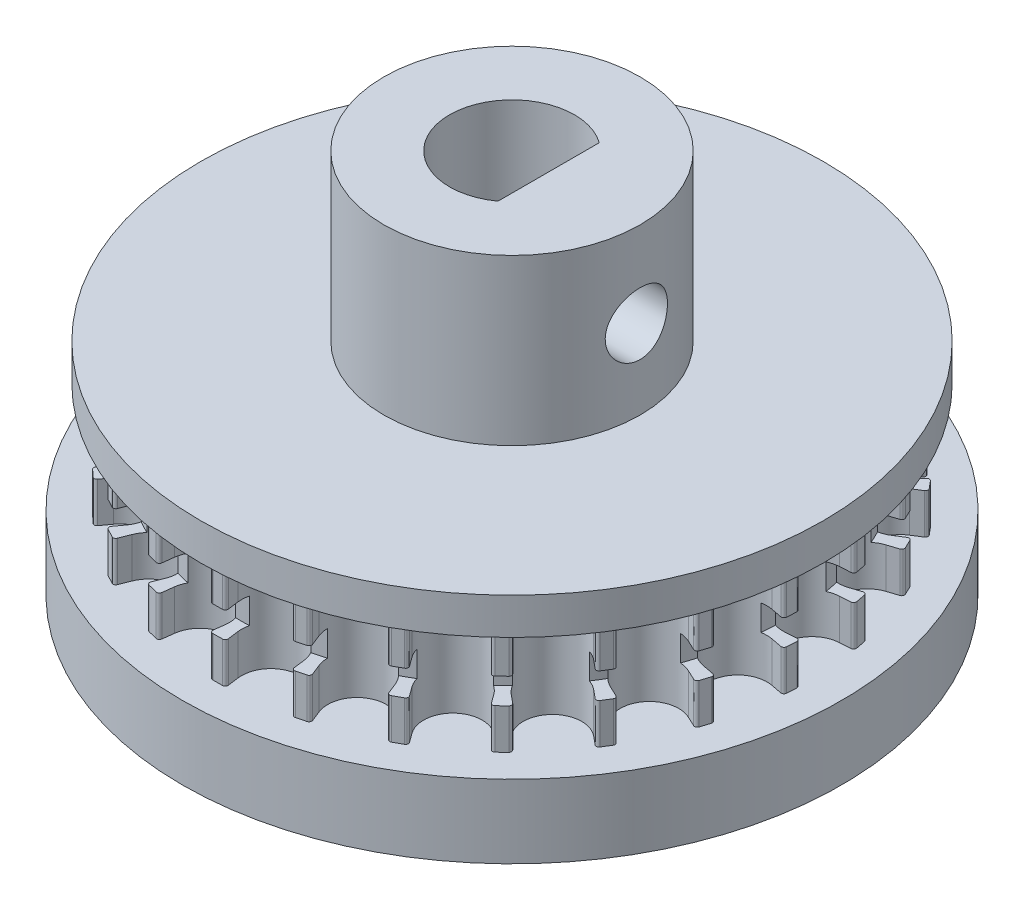
SolidWorks part; units mm, degrees
ref_plane "Спереди" through (0, 0, 0) normal (0, 0, 1) x (1, 0, 0)
ref_plane "Сверху" through (0, 0, 0) normal (0, 1, 0) x (1, 0, 0)
ref_plane "Справа" through (0, 0, 0) normal (1, 0, 0) x (0, 0, -1)
sketch "Sketch1" plane through (0, 0, 0) normal (0, 1, 0) x (1, 0, 0)
  circle A0 centre (0, 0) radius 18
extrude "Boss-Extrude1" add sketch "Sketch1" along normal blind 4
sketch "Sketch7" plane through (0, 4, 0) normal (0, 1, 0) x (1, 0, 0)
  line L25 (2.2991, 15.8675) -> (2.15, 15.2867)
  line L26 (5.4051, 15.097) -> (5.2495, 14.4909)
  line L27 (6.173, 14.7972) -> (5.8841, 14.2718)
  line L28 (-1.7192, 15.9408) -> (-1.7192, 15.3411)
  line L29 (1.4808, 15.9669) -> (1.4808, 15.3411)
  line L30 (8.9898, 13.2785) -> (8.6883, 12.7302)
  line L31 (9.659, 12.7972) -> (9.2485, 12.3601)
  line L32 (12.0096, 10.6257) -> (11.5812, 10.1695)
  line L33 (12.5381, 9.9931) -> (12.0318, 9.6717)
  line L34 (14.2748, 7.3052) -> (13.7464, 6.9699)
  line L35 (14.6293, 6.561) -> (14.059, 6.3757)
  line L36 (15.6431, 3.5257) -> (15.0479, 3.3323)
  line L37 (15.8014, 2.7167) -> (15.2029, 2.6791)
  line L38 (16.0284, -0.4753) -> (15.4038, -0.5146)
  line L39 (15.9806, -1.2983) -> (15.3915, -1.1859)
  line L40 (15.4066, -4.4465) -> (14.7919, -4.3292)
  line L41 (15.1556, -5.2317) -> (14.6131, -4.9764)
  line L42 (13.8168, -8.1383) -> (13.2506, -7.8718)
  line L43 (13.3784, -8.8364) -> (12.9164, -8.4542)
  line L44 (11.3588, -11.3187) -> (10.8766, -10.9198)
  line L45 (10.7606, -11.8859) -> (10.4081, -11.4007)
  line L46 (8.1871, -13.7879) -> (7.8193, -13.2816)
  line L47 (7.4666, -14.1885) -> (7.2459, -13.631)
  line L48 (4.501, -15.3908) -> (4.2706, -14.809)
  line L49 (3.7035, -15.5996) -> (3.6284, -15.0047)
  line L50 (0.532, -16.0266) -> (0.4536, -15.4058)
  line L51 (-0.2923, -16.0306) -> (-0.2171, -15.4356)
  line L52 (-3.4703, -15.6554) -> (-3.3919, -15.0346)
  line L53 (-4.2697, -15.4542) -> (-4.049, -14.8967)
  line L54 (-7.2547, -14.3006) -> (-7.0243, -13.7187)
  line L55 (-7.9789, -13.9069) -> (-7.6265, -13.4218)
  line L56 (-10.5831, -12.0471) -> (-10.2153, -11.5408)
  line L57 (-11.1867, -11.4857) -> (-10.7247, -11.1035)
  line L58 (-13.2466, -9.0367) -> (-12.7645, -8.6378)
  line L59 (-13.6917, -8.3428) -> (-13.1491, -8.0875)
  line L60 (-15.0778, -5.4585) -> (-14.5116, -5.1921)
  line L61 (-15.3363, -4.6757) -> (-14.7473, -4.5634)
  line L62 (-15.9616, -1.5373) -> (-15.3469, -1.4201)
  line L63 (-16.0173, -0.7149) -> (-15.4188, -0.7525)
  line L64 (-15.8424, 2.4805) -> (-15.2179, 2.4412)
  line L65 (-15.6918, 3.2909) -> (-15.1215, 3.1056)
  line L66 (-14.7279, 6.3424) -> (-14.1327, 6.149)
  line L67 (-14.3804, 7.0899) -> (-13.8741, 6.7686)
  line L68 (-12.6879, 9.8058) -> (-12.1595, 9.4705)
  line L69 (-12.1654, 10.4435) -> (-11.755, 10.0064)
  line L70 (-9.8506, 12.6531) -> (-9.4223, 12.1969)
  line L71 (-9.1861, 13.1408) -> (-8.8972, 12.6153)
  line L72 (-6.3945, 14.7053) -> (-6.093, 14.1569)
  line L73 (-5.6295, 15.0124) -> (-5.4804, 14.4316)
  line L74 (-2.5365, 15.8336) -> (-2.3809, 15.2274)
  line L75 (1.6461, 16.1162) -> (2.174, 16.0535)
  line L76 (5.6023, 15.2005) -> (6.098, 15.0085)
  line L77 (9.2065, 13.3297) -> (9.6389, 13.0204)
  line L78 (12.2322, 10.6214) -> (12.5741, 10.2143)
  line L79 (14.4893, 7.2457) -> (14.7193, 6.7663)
  line L80 (15.836, 3.4147) -> (15.9396, 2.8932)
  line L81 (16.1877, -0.6309) -> (16.1583, -1.1617)
  line L82 (15.5223, -4.6368) -> (15.3618, -5.1436)
  line L83 (13.8815, -8.3513) -> (13.6, -8.8023)
  line L84 (11.3685, -11.5411) -> (10.9837, -11.9079)
  line L85 (8.1411, -14.0058) -> (7.6772, -14.2654)
  line L86 (4.4023, -15.5904) -> (3.8884, -15.7264)
  line L87 (0.3868, -16.1954) -> (-0.1448, -16.1994)
  line L88 (-3.653, -15.7828) -> (-4.1689, -15.6544)
  line L89 (-7.4632, -14.3785) -> (-7.931, -14.1258)
  line L90 (-10.8045, -12.0707) -> (-11.1948, -11.7097)
  line L91 (-13.467, -9.0045) -> (-13.7552, -8.5578)
  line L92 (-15.2832, -5.3725) -> (-15.4512, -4.8682)
  line L93 (-16.1391, -1.403) -> (-16.1765, -0.8726)
  line L94 (-15.981, 2.6548) -> (-15.8853, 3.1777)
  line L95 (-14.8187, 6.5457) -> (-14.596, 7.0284)
  line L96 (-12.7253, 10.0253) -> (-12.3895, 10.4374)
  line L97 (-9.8323, 12.875) -> (-9.4046, 13.1907)
  line L98 (-6.3216, 14.9157) -> (-5.8287, 15.1151)
  line L99 (-2.4136, 16.0192) -> (-1.8866, 16.0898)
  arc A16 (13.7013, 6.2878) -> (13.8151, 6.4563) centre (13.6668, 6.4337) ccw
  arc A75 (-1.7192, 15.3411) -> (1.4808, 15.3411) centre (-0.1192, 15.3411) ccw
  arc A76 (2.2991, 15.8675) -> (2.174, 16.0535) centre (2.1539, 15.9048) ccw
  arc A77 (-1.7192, 15.9408) -> (-1.8866, 16.0898) centre (-1.8692, 15.9408) ccw
  arc A78 (1.6461, 16.1162) -> (1.4808, 15.9669) centre (1.6308, 15.9669) ccw
  arc A79 (2.15, 15.2867) -> (5.2495, 14.4909) centre (3.6998, 14.8888) ccw
  arc A80 (5.6023, 15.2005) -> (5.4051, 15.097) centre (5.5504, 15.0597) ccw
  arc A81 (6.173, 14.7972) -> (6.098, 15.0085) centre (6.0416, 14.8695) ccw
  arc A82 (5.8841, 14.2718) -> (8.6883, 12.7302) centre (7.2862, 13.501) ccw
  arc A83 (9.2065, 13.3297) -> (8.9898, 13.2785) centre (9.1212, 13.2063) ccw
  arc A84 (9.659, 12.7972) -> (9.6389, 13.0204) centre (9.5496, 12.8999) ccw
  arc A85 (9.2485, 12.3601) -> (11.5812, 10.1695) centre (10.4149, 11.2648) ccw
  arc A86 (12.2322, 10.6214) -> (12.0096, 10.6257) centre (12.1189, 10.523) ccw
  arc A87 (12.5381, 9.9931) -> (12.5741, 10.2143) centre (12.4577, 10.1197) ccw
  arc A88 (12.0318, 9.6717) -> (13.7464, 6.9699) centre (12.8891, 8.3208) ccw
  arc A89 (14.4893, 7.2457) -> (14.2748, 7.3052) centre (14.3552, 7.1786) ccw
  arc A90 (14.6293, 6.561) -> (14.7193, 6.7663) centre (14.583, 6.7037) ccw
  arc A91 (14.059, 6.3757) -> (15.0479, 3.3323) centre (14.5535, 4.854) ccw
  arc A92 (15.836, 3.4147) -> (15.6431, 3.5257) centre (15.6894, 3.3831) ccw
  arc A93 (15.8014, 2.7167) -> (15.9396, 2.8932) centre (15.792, 2.8664) ccw
  arc A94 (15.2029, 2.6791) -> (15.4038, -0.5146) centre (15.3034, 1.0822) ccw
  arc A95 (16.1877, -0.6309) -> (16.0284, -0.4753) centre (16.0378, -0.625) ccw
  arc A96 (15.9806, -1.2983) -> (16.1583, -1.1617) centre (16.0087, -1.1509) ccw
  arc A97 (15.3915, -1.1859) -> (14.7919, -4.3292) centre (15.0917, -2.7576) ccw
  arc A98 (15.5223, -4.6368) -> (15.4066, -4.4465) centre (15.3785, -4.5938) ccw
  arc A99 (15.1556, -5.2317) -> (15.3618, -5.1436) centre (15.2195, -5.096) ccw
  arc A100 (14.6131, -4.9764) -> (13.2506, -7.8718) centre (13.9318, -6.4241) ccw
  arc A101 (13.8815, -8.3513) -> (13.8168, -8.1383) centre (13.7529, -8.274) ccw
  arc A102 (13.3784, -8.8364) -> (13.6, -8.8023) centre (13.474, -8.7208) ccw
  arc A103 (12.9164, -8.4542) -> (10.8766, -10.9198) centre (11.8965, -9.687) ccw
  arc A104 (11.3685, -11.5411) -> (11.3588, -11.3187) centre (11.2632, -11.4343) ccw
  arc A105 (10.7606, -11.8859) -> (10.9837, -11.9079) centre (10.882, -11.7977) ccw
  arc A106 (10.4081, -11.4007) -> (7.8193, -13.2816) centre (9.1137, -12.3412) ccw
  arc A107 (8.1411, -14.0058) -> (8.1871, -13.7879) centre (8.0658, -13.8761) ccw
  arc A108 (7.4666, -14.1885) -> (7.6772, -14.2654) centre (7.6061, -14.1333) ccw
  arc A109 (7.2459, -13.631) -> (4.2706, -14.809) centre (5.7583, -14.22) ccw
  arc A110 (4.4023, -15.5904) -> (4.501, -15.3908) centre (4.3615, -15.446) ccw
  arc A111 (3.7035, -15.5996) -> (3.8884, -15.7264) centre (3.8524, -15.5808) ccw
  arc A112 (3.6284, -15.0047) -> (0.4536, -15.4058) centre (2.041, -15.2052) ccw
  arc A113 (0.3868, -16.1954) -> (0.532, -16.0266) centre (0.3832, -16.0454) ccw
  arc A114 (-0.2923, -16.0306) -> (-0.1448, -16.1994) centre (-0.1435, -16.0494) ccw
  arc A115 (-0.2171, -15.4356) -> (-3.3919, -15.0346) centre (-1.8045, -15.2351) ccw
  arc A116 (-3.653, -15.7828) -> (-3.4703, -15.6554) centre (-3.6191, -15.6366) ccw
  arc A117 (-4.2697, -15.4542) -> (-4.1689, -15.6544) centre (-4.1303, -15.5095) ccw
  arc A118 (-4.049, -14.8967) -> (-7.0243, -13.7187) centre (-5.5366, -14.3077) ccw
  arc A119 (-7.4632, -14.3785) -> (-7.2547, -14.3006) centre (-7.3941, -14.2453) ccw
  arc A120 (-7.9789, -13.9069) -> (-7.931, -14.1258) centre (-7.8576, -13.995) ccw
  arc A121 (-7.6265, -13.4218) -> (-10.2153, -11.5408) centre (-8.9209, -12.4813) ccw
  arc A122 (-10.8045, -12.0707) -> (-10.5831, -12.0471) centre (-10.7045, -11.9589) ccw
  arc A123 (-11.1867, -11.4857) -> (-11.1948, -11.7097) centre (-11.0911, -11.6013) ccw
  arc A124 (-10.7247, -11.1035) -> (-12.7645, -8.6378) centre (-11.7446, -9.8706) ccw
  arc A125 (-13.467, -9.0045) -> (-13.2466, -9.0367) centre (-13.3423, -8.9211) ccw
  arc A126 (-13.6917, -8.3428) -> (-13.7552, -8.5578) centre (-13.6278, -8.4785) ccw
  arc A127 (-13.1491, -8.0875) -> (-14.5116, -5.1921) centre (-13.8303, -6.6398) ccw
  arc A128 (-15.2832, -5.3725) -> (-15.0778, -5.4585) centre (-15.1417, -5.3228) ccw
  arc A129 (-15.3363, -4.6757) -> (-15.4512, -4.8682) centre (-15.3082, -4.8231) ccw
  arc A130 (-14.7473, -4.5634) -> (-15.3469, -1.4201) centre (-15.0471, -2.9917) ccw
  arc A131 (-16.1391, -1.403) -> (-15.9616, -1.5373) centre (-15.9897, -1.39) ccw
  arc A132 (-16.0173, -0.7149) -> (-16.1765, -0.8726) centre (-16.0267, -0.8646) ccw
  arc A133 (-15.4188, -0.7525) -> (-15.2179, 2.4412) centre (-15.3184, 0.8443) ccw
  arc A134 (-15.981, 2.6548) -> (-15.8424, 2.4805) centre (-15.833, 2.6302) ccw
  arc A135 (-15.6918, 3.2909) -> (-15.8853, 3.1777) centre (-15.7382, 3.1483) ccw
  arc A136 (-15.1215, 3.1056) -> (-14.1327, 6.149) centre (-14.6271, 4.6273) ccw
  arc A137 (-14.8187, 6.5457) -> (-14.7279, 6.3424) centre (-14.6815, 6.4851) ccw
  arc A138 (-14.3804, 7.0899) -> (-14.596, 7.0284) centre (-14.4608, 6.9633) ccw
  arc A139 (-13.8741, 6.7686) -> (-12.1595, 9.4705) centre (-13.0168, 8.1196) ccw
  arc A140 (-12.7253, 10.0253) -> (-12.6879, 9.8058) centre (-12.6075, 9.9325) ccw
  arc A141 (-12.1654, 10.4435) -> (-12.3895, 10.4374) centre (-12.2748, 10.3408) ccw
  arc A142 (-11.755, 10.0064) -> (-9.4223, 12.1969) centre (-10.5886, 11.1016) ccw
  arc A143 (-9.8323, 12.875) -> (-9.8506, 12.6531) centre (-9.7413, 12.7558) ccw
  arc A144 (-9.1861, 13.1408) -> (-9.4046, 13.1907) centre (-9.3175, 13.0685) ccw
  arc A145 (-8.8972, 12.6153) -> (-6.093, 14.1569) centre (-7.4951, 13.3861) ccw
  arc A146 (-6.3216, 14.9157) -> (-6.3945, 14.7053) centre (-6.263, 14.7776) ccw
  arc A147 (-5.6295, 15.0124) -> (-5.8287, 15.1151) centre (-5.7748, 14.9751) ccw
  arc A148 (-5.4804, 14.4316) -> (-2.3809, 15.2274) centre (-3.9306, 14.8295) ccw
  arc A149 (-2.4136, 16.0192) -> (-2.5365, 15.8336) centre (-2.3912, 15.8709) ccw
  point P179 (0, 0)
  point P228 (0, 0)
  point P406 (0, 0)
  point P455 (0, 0)
  dimension "D5" = 25
  dimension "D6" = 25
extrude "Boss-Extrude4" add sketch "Sketch7" along normal blind 6 contours L99 A149 L74 A148 L73 A147 L98 A146 L72 A145 L71 A144 L97 A143 L70 A142 L69 A141 L96 A140 L68 A139 L67 A138 L95 A137 L66 A136 L65 A135 L94 A134 L64 A133 L63 A132 L93 A131 L62 A130 L61 A129 L92 A128 L60 A127 L59 A126 region at (0, 4, 0)
sketch "Sketch8" plane through (0, 10, 0) normal (0, 1, 0) x (1, 0, 0)
  circle A0 centre (0, 0) radius 17
extrude "Boss-Extrude5" add sketch "Sketch8" along normal blind 2
sketch "Sketch9" plane through (0, 12, 0) normal (0, 1, 0) x (1, 0, 0)
  circle A0 centre (0, 0) radius 7
extrude "Boss-Extrude6" add sketch "Sketch9" along normal blind 9
sketch "Sketch10" plane through (0, 21, 0) normal (0, 1, 0) x (1, 0, 0)
  line L1 (2, 0) -> (2, 2.7641)
  line L2 (2, 2.7641) -> (2, -2.7641)
  arc A0 (2, 2.7641) -> (2, -2.7641) centre (0, 0) ccw
extrude "Cut-Extrude3" cut sketch "Sketch10" against normal through all contours L1 A0 L2 region at (-0.4527, 21, 0)
ref_plane "Plane3" through (0, 21, 0) normal (0, 1, 0) x (1, 0, 0)
sketch3d "3DSketch1"
  circle A0 centre (0, 16.327, 0) radius 1.7
  point P2 (-1.7, 16.327, 0)
extrude "Cut-Extrude4" cut sketch "3DSketch1" along direction (1, 0, 0) on the side of the normal blind 9
ref_plane "Plane6" through (0, 7.6, 0) normal (0, 1, 0) x (1, 0, 0)
sketch "Sketch17" plane through (0, 7.6, 0) normal (0, 1, 0) x (1, 0, 0)
  circle A0 centre (0, 0) radius 17.0167
  circle A1 centre (0, 0) radius 14.8366
extrude "Cut-Extrude6" cut sketch "Sketch17" against normal blind 1.4
